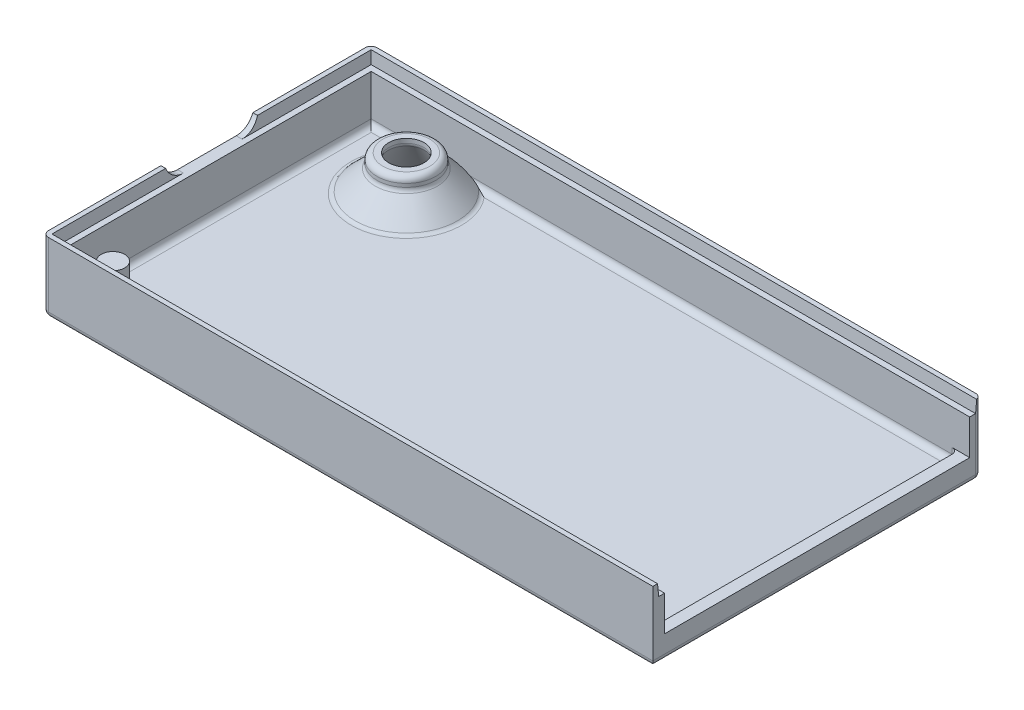
SolidWorks part; units mm, degrees
ref_plane "Спереди" through (0, 0, 0) normal (0, 0, 1) x (1, 0, 0)
ref_plane "Сверху" through (0, 0, 0) normal (0, 1, 0) x (1, 0, 0)
ref_plane "Справа" through (0, 0, 0) normal (1, 0, 0) x (0, 0, -1)
sketch "Эскиз1" plane through (0, 0, 0) normal (0, 1, 0) x (1, 0, 0)
  line L1 (-26, 14) -> (26, 14)
  line L2 (-26, 14) -> (-26, -14)
  line L3 (-26, -14) -> (26, -14)
  line L4 (26, 14) -> (26, -14)
  line L5 (-26, 14) -> (26, -14) construction
  line L6 (-26, -14) -> (26, 14) construction
  point P0 (0, 0)
  dimension "D1" = 28
  dimension "D2" = 52
extrude "Бобышка-Вытянуть1" add sketch "Эскиз1" along normal blind 6
sketch "Эскиз2" plane through (0, 6, 0) normal (0, 1, 0) x (1, 0, 0)
  line L0 (26, 14) -> (-26, 14) construction
  line L1 (-25, 13) -> (25, 13)
  line L2 (-25, 13) -> (-25, -13)
  line L3 (-25, -13) -> (25, -13)
  line L4 (25, 13) -> (25, -13)
  line L5 (-25, 13) -> (25, -13) construction
  line L6 (-25, -13) -> (25, 13) construction
  line L7 (-26, 14) -> (-26, -14) construction
  point P0 (0, 0)
  dimension "D1" = 1
  dimension "D2" = 1
extrude "Вырез-Вытянуть1" cut sketch "Эскиз2" against normal blind 5
sketch "Эскиз3" plane through (0, 6, 0) normal (0, 1, 0) x (1, 0, 0)
  line L0 (26, -14) -> (26, 14) construction
  line L1 (25, 13) -> (26, 13)
  line L2 (25, 13) -> (25, -13)
  line L3 (25, -13) -> (26, -13)
  line L4 (26, 13) -> (26, -13)
  line L5 (-25, -13) -> (25, -13) construction
extrude "Вырез-Вытянуть2" cut sketch "Эскиз3" against normal blind 4
sketch "Эскиз4" plane through (-26, 0, 0) normal (-1, 0, 0) x (0, 0, 1)
  line L0 (-2.5, 6.5) -> (2.5, 6.5) construction
  line L1 (-2.5, 8) -> (2.5, 8)
  line L2 (-2.5, 5) -> (2.5, 5)
  line L3 (-14, 6) -> (14, 6) construction
  line L4 (-4, 9.8341) -> (-4, 5) construction
  line L5 (4, 9.8341) -> (4, 4.5024) construction
  arc A0 (-2.5, 8) -> (-2.5, 5) centre (-2.5, 6.5) ccw
  arc A1 (2.5, 5) -> (2.5, 8) centre (2.5, 6.5) ccw
  point P2 (0, 6.5)
  dimension "D1" = 3
  dimension "D2" = 2
  dimension "D3" = 8
extrude "Вырез-Вытянуть3" cut sketch "Эскиз4" against normal up to next
sketch "Эскиз6" plane through (0, 1, 0) normal (0, 1, 0) x (1, 0, 0)
  line L0 (-25, 13) -> (-25, -13) construction
  line L2 (26, 13) -> (-25, 13) construction
  circle A0 centre (-18.5, 9.5) radius 1.5
  dimension "D1" = 3
  dimension "D2" = 6.5
  dimension "D3" = 3.5
extrude "Вырез-Вытянуть4" cut sketch "Эскиз6" against normal blind 4
sketch "Эскиз7" plane through (0, 1, 0) normal (0, 1, 0) x (1, 0, 0)
  line L0 (-25, 13) -> (-25, -13) construction
  line L2 (-25, -13) -> (26, -13) construction
  circle A1 centre (-18.5, 9.5) radius 1.5 construction
  circle A2 centre (-18.5, 9.5) radius 2.5
  circle A3 centre (-18.5, 9.5) radius 2.5
  circle A4 centre (-18.5, 9.5) radius 1.5
  circle A5 centre (-23, -11) radius 1
  dimension "D2" = 2
  dimension "D3" = 2
  dimension "D4" = 2
  dimension "D1" = 1
extrude "Бобышка-Вытянуть3" add sketch "Эскиз7" along normal blind 3
chamfer "Фаска2" distance 2 angle 45 1 edges at (-18.5, 1, -7)
chamfer "Фаска3" distance 3.5 distance2 2 1 edges at (-18.5, 0, -8)
fillet "Скругление1" radius 0.5 19 edges at (-25, 1, 0) (4.6642, 1, -13) (-23.1642, 1, -13) (25, 1, 0) (0, 1, 13) (-18.5, 1, -5) (0, 0, -14) (-26, 0, 0) (0, 0, 14) (26, 0, 0) (-18.5, 0, -6) (-18.5, 4, -7) (-18.5, 3, -7) (25, 1.5, -13) (25, 1.5, 13) (26, 3, -14) (-26, 3, -14) (-26, 3, 14) (-18.5, 3.5, -8)
fillet "Скругление2" radius 0.5 1 edges at (-23, 1, 12)
sketch "Эскиз9" plane through (0, 4, 0) normal (0, 1, 0) x (1, 0, 0)
  line L0 (-23, -11) -> (-23, -13) construction
  line L1 (-23, -11) -> (-25, -11) construction
  line L2 (-23.4, -13) -> (-23.4, -11)
  line L3 (-23.4, -13) -> (-22.6, -13)
  line L4 (-23.4, -11) -> (-22.6, -11)
  line L5 (-22.6, -13) -> (-22.6, -11)
  line L6 (-23.4, -13) -> (-22.6, -11) construction
  line L7 (-23.4, -11) -> (-22.6, -13) construction
  line L9 (-25, -11) -> (-25, -11.4)
  line L10 (-25, -11.4) -> (-23, -11.4)
  line L11 (-23, -11.4) -> (-23, -11)
  line L12 (-23, -11) -> (-23, -10.6)
  line L13 (-23, -10.6) -> (-25, -10.6)
  line L14 (-25, -10.6) -> (-25, -11)
  line L15 (-25, 13) -> (-25, 3.9142) construction
  line L16 (-25, -13) -> (26, -13) construction
  point P5 (-23, -12)
  circle M12 centre (-23, -11) radius 1
  dimension "D1" = 0.8
  dimension "D2" = 0.8
extrude "Бобышка-Вытянуть4" add sketch "Эскиз9" against normal up to next from offset 1 contours L13 L14 L9 L10 M12 | L2 L13 L10 L11 L4 M12 | L12 L13 L2 L4 | L3 L5 L2 M12 | L11 L10 L2 L5 L4 M12 offset against normal yes
sketch "Эскиз10" plane through (0, 6, 0) normal (0, 1, 0) x (1, 0, 0)
  line L0 (26, 13) -> (26, 13.5)
  line L1 (-25.5, -13.5) -> (-25.5, 13.5)
  line L2 (-25.5, 13.5) -> (26, 13.5)
  line L4 (-25.5, 0) -> (-25, 0)
  line L5 (-25, -13) -> (-25, 13)
  line L6 (-25, 13) -> (26, 13)
  line L7 (0, 0) -> (-37.9229, 0) construction
  line L8 (-25, -13) -> (26, -13)
  line L9 (-25.5, -13.5) -> (26, -13.5)
  line L10 (26, -13) -> (26, -13.5)
  line M14 (26, -14) -> (26, -13)
  line M15 (26, -13) -> (-25, -13)
  line M16 (-25, -13) -> (-25, -3.9142)
  line M17 (-25, -3.9142) -> (-26, -3.9142)
  dimension "D1" = 0.5
extrude "Вырез-Вытянуть5" cut sketch "Эскиз10" against normal blind 1 contours L1 L9 M14 M15 M16 M17 | L5 L4 L1 M17
chamfer "Фаска4" distance 1 distance2 0.1 4 edges at (-25.5, 6, -8.7071) (0.25, 6, -13.5) (0.25, 6, 13.5) (-25.5, 6, 8.7071)
